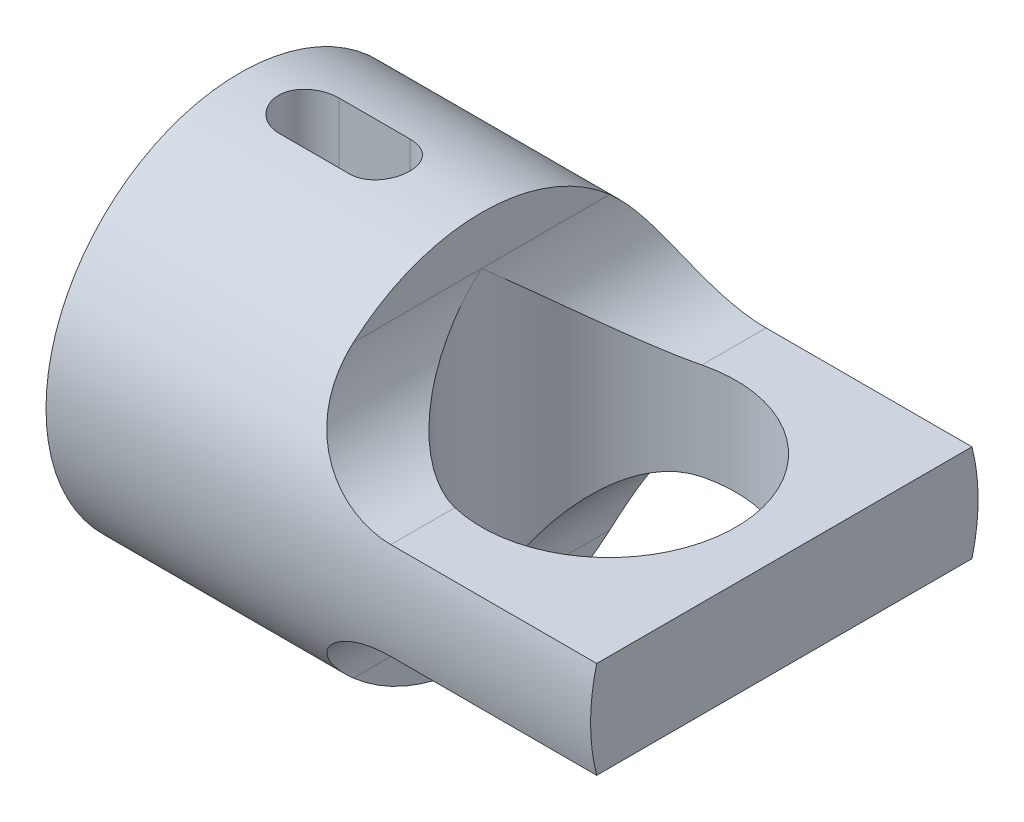
SolidWorks part; units mm, degrees
note: The reader was unsure of these and kept them because the rebuilt part matched: shared geometry of "Sketch2<3>".
material "AISI 4340 Steel, annealed"
ref_plane "Front Plane" through (0, 0, 0) normal (0, 0, 1) x (1, 0, 0)
ref_plane "Top Plane" through (0, 0, 0) normal (0, 1, 0) x (1, 0, 0)
ref_plane "Right Plane" through (0, 0, 0) normal (1, 0, 0) x (0, 0, -1)
sketch "Sketch1" plane through (0, 0, 0) normal (0, 1, 0) x (1, 0, 0)
  line L0 (0, 0) -> (0, 558.8) construction
  line L1 (355.6, -292.1) -> (-355.6, -292.1)
  line L2 (355.6, -292.1) -> (355.6, 292.1)
  line L3 (355.6, 292.1) -> (-355.6, 292.1)
  line L4 (-355.6, -292.1) -> (-355.6, 292.1)
  line L5 (355.6, -292.1) -> (-355.6, 292.1) construction
  line L6 (355.6, 292.1) -> (-355.6, -292.1) construction
  line L7 (-355.6, 508) -> (355.6, 508)
  line L8 (-355.6, 508) -> (-355.6, 558.8)
  line L9 (-355.6, 558.8) -> (355.6, 558.8)
  line L10 (355.6, 508) -> (355.6, 558.8)
  line L11 (-355.6, 508) -> (-355.6, 292.1) construction
  line L12 (355.6, 508) -> (355.6, 292.1) construction
  line L13 (-355.6, 0) -> (355.6, 0) construction
  line L14 (-294.9829, 0) -> (-294.9829, 558.8) construction
  line L15 (294.9829, 0) -> (294.9829, 558.8) construction
  line L16 (-294.9829, 534.9875) -> (0, 531.8125) construction
  line L17 (-294.7945, 552.4935) -> (0.1884, 549.3185)
  line L18 (-295.1713, 517.4815) -> (-0.1884, 514.3065)
  line L19 (0, 531.8125) -> (294.9829, 534.9875) construction
  line L20 (-0.1884, 549.3185) -> (294.7945, 552.4935)
  line L21 (0.1884, 514.3065) -> (295.1713, 517.4815)
  line L22 (-355.6, 292.1) -> (-355.6, 342.9)
  line L23 (-358.775, 342.9) -> (-330.2, 342.9)
  line L24 (-330.2, 342.9) -> (-330.2, 292.1)
  line L25 (-101.6, 558.8) -> (-101.6, 0) construction
  line L26 (-333.0829, 293.6875) -> (-256.8829, 293.6875)
  line L27 (-333.0829, 293.6875) -> (-333.0829, 331.7875)
  line L28 (-333.0829, 331.7875) -> (-256.8829, 331.7875)
  line L29 (-256.8829, 293.6875) -> (-256.8829, 331.7875)
  line L30 (-333.0829, 293.6875) -> (-256.8829, 331.7875) construction
  line L31 (-333.0829, 331.7875) -> (-256.8829, 293.6875) construction
  line L32 (358.775, 342.9) -> (0, 380.3316)
  line L33 (-330.2, 326.4184) -> (0, 361.1763)
  line L34 (-114.3, 292.1) -> (-114.3, 368.3)
  line L35 (-355.6, 558.8) -> (-355.6, 762) construction
  line L36 (-88.9, 292.1) -> (-88.9, 368.3)
  line L37 (-114.3, 292.1) -> (-88.9, 368.3) construction
  line L38 (-114.3, 368.3) -> (-88.9, 292.1) construction
  line L39 (330.2, 326.726) -> (0, 361.1763)
  line L40 (-355.6, 762) -> (355.6, 762)
  line L41 (-355.6, 241.3) -> (355.6, 241.3)
  line L42 (-330.2, 342.9) -> (-330.2, 561.975) construction
  line L43 (-38.1, 293.6875) -> (38.1, 293.6875)
  line L44 (-38.1, 293.6875) -> (-38.1, 357.1875)
  line L45 (-38.1, 357.1875) -> (38.1, 357.1875)
  line L46 (38.1, 293.6875) -> (38.1, 357.1875)
  line L47 (-38.1, 293.6875) -> (38.1, 357.1875) construction
  line L48 (-38.1, 357.1875) -> (38.1, 293.6875) construction
  line L49 (-330.2, 561.975) -> (-358.775, 561.975)
  line L50 (-358.775, 342.9) -> (-358.775, -342.9)
  line L51 (-355.6, 579.4375) -> (358.775, 579.4375)
  line L52 (-330.2, 292.1) -> (-330.2, -342.9)
  line L53 (-330.2, -342.9) -> (-358.775, -342.9)
  line L54 (-355.6, 342.9) -> (0, 380.3316)
  line L55 (-330.2, 326.4184) -> (-355.6, 323.7448) construction
  line L56 (-114.3, 368.3) -> (-88.9, 368.3)
  line L57 (330.2, 292.1) -> (330.2, 342.9)
  line L58 (330.2, 342.9) -> (358.775, 342.9)
  line L59 (358.775, 342.9) -> (358.775, -342.9)
  line L60 (330.2, 342.9) -> (330.2, 561.975)
  line L61 (330.2, 561.975) -> (358.775, 561.975)
  line L62 (358.775, -342.9) -> (330.2, -342.9)
  line L63 (330.2, -342.9) -> (330.2, -292.1)
  line L64 (355.6, 762) -> (355.6, 558.8) construction
  line L65 (-355.6, 762) -> (-355.6, 812.8)
  line L66 (-355.6, 812.8) -> (355.6, 812.8)
  line L67 (355.6, 812.8) -> (355.6, 762)
  line L68 (-21.2236, 223.9178) -> (-84.7236, 223.9178)
  line L69 (-21.2236, 223.9178) -> (-21.2236, 333.1378)
  line L70 (-21.2236, 333.1378) -> (-84.7236, 333.1378)
  line L71 (-84.7236, 223.9178) -> (-84.7236, 333.1378)
  line L72 (-312.49, 247.65) -> (-277.4759, 247.65)
  line L73 (-312.49, 247.65) -> (-312.49, 285.75)
  line L74 (-312.49, 285.75) -> (-277.4759, 285.75)
  line L75 (-277.4759, 247.65) -> (-277.4759, 285.75)
  line L76 (-312.49, 247.65) -> (-277.4759, 285.75) construction
  line L77 (-312.49, 285.75) -> (-277.4759, 247.65) construction
  line L78 (-114.3, 598.4875) -> (-355.6, 598.4875)
  line L79 (-355.6, 598.4875) -> (-355.6, 579.4375)
  line L80 (-114.3, 508) -> (-114.3, 598.4875)
  line L81 (-114.3, 598.4875) -> (-88.9, 598.4875)
  line L82 (-88.9, 508) -> (-88.9, 598.4875)
  line L83 (-114.3, 508) -> (-88.9, 598.4875) construction
  line L84 (-114.3, 598.4875) -> (-88.9, 508) construction
  line L85 (358.775, 579.4375) -> (358.775, 598.4875)
  line L86 (-88.9, 598.4875) -> (358.775, 598.4875)
  line L87 (358.775, 561.975) -> (358.775, 504.825)
  line L88 (358.775, 504.825) -> (-358.775, 504.825)
  line L89 (-358.775, 504.825) -> (-358.775, 561.975)
  line L90 (-355.6, 558.8) -> (-358.775, 558.8)
  line L91 (-355.6, 292.1) -> (-355.6, 342.9)
  line L92 (-355.6, 292.1) -> (-358.775, 292.1)
  line L93 (355.6, 558.8) -> (358.775, 558.8)
  line L94 (-355.6, -292.1) -> (-358.775, -292.1)
  line L95 (-355.6, -292.1) -> (-355.6, -342.9)
  line L96 (355.6, -292.1) -> (358.775, -292.1)
  line L97 (355.6, -292.1) -> (355.6, -342.9)
  line L98 (0, 531.8125) -> (0, 812.8) construction
  line L99 (-294.9829, 534.9875) -> (-294.9829, 812.8) construction
  line L100 (294.9829, 534.9875) -> (294.9829, 812.8) construction
  line L101 (-355.6, 751.5377) -> (355.6, 743.8829) construction
  line L102 (355.6, 751.5377) -> (0, 747.7103) construction
  line L103 (224.9153, 774.1325) -> (294.9829, 788.9875)
  line L104 (-355.6, 753.5075) -> (355.6, 722.339) construction
  line L105 (0, 785.8125) -> (-2.0947, 738.015) construction
  line L106 (224.9153, 774.1325) -> (177.8, 788.9875) construction
  line L107 (223.1136, 769.3102) -> (177.8, 788.9875) construction
  line L108 (211.3067, 752.6857) -> (177.8, 788.9875) construction
  line L109 (131.699, 840.6975) -> (135.001, 840.6975)
  line L110 (224.9153, 774.1325) -> (211.3067, 752.6857)
  line L111 (177.8, 788.9875) -> (177.8, 838.3891) construction
  line L112 (218.111, 763.4091) -> (177.8, 788.9875) construction
  line L113 (190.5, 836.7288) -> (165.1, 836.7288)
  line L114 (165.1, 836.7288) -> (177.8, 788.9875)
  line L115 (177.8, 788.9875) -> (190.5, 836.7288)
  line L116 (355.6, 812.8) -> (355.6, 852.4875)
  line L117 (355.6, 852.4875) -> (330.2, 852.4875)
  line L118 (330.2, 852.4875) -> (330.2, 812.8)
  line L119 (261.0328, 817.6788) -> (294.9829, 788.9875)
  line L120 (114.3, 852.4875) -> (88.9, 852.4875)
  line L121 (114.3, 852.4875) -> (114.3, 762)
  line L122 (218.2338, 855.7788) -> (257.8578, 855.7788)
  line L123 (88.9, 852.4875) -> (88.9, 762)
  line L124 (114.3, 852.4875) -> (88.9, 762) construction
  line L125 (114.3, 762) -> (88.9, 852.4875) construction
  line L126 (218.2338, 855.7788) -> (218.2338, 817.6788)
  line L127 (218.2338, 817.6788) -> (257.8578, 817.6788)
  line L128 (257.8578, 855.7788) -> (257.8578, 817.6788)
  line L129 (218.2338, 855.7788) -> (257.8578, 817.6788) construction
  line L130 (218.2338, 817.6788) -> (257.8578, 855.7788) construction
  line L131 (261.0328, 836.7288) -> (355.6, 836.7288)
  line L132 (261.0328, 840.6975) -> (355.6, 840.6975)
  line L133 (261.0328, 832.76) -> (355.6, 832.76)
  line L134 (257.8578, 817.6788) -> (261.0328, 817.6788)
  line L135 (261.0328, 817.6788) -> (261.0328, 855.7788)
  line L136 (261.0328, 855.7788) -> (257.8578, 855.7788)
  line L137 (294.9829, 827.0875) -> (294.9829, 832.76)
  line L138 (261.0328, 846.2538) -> (270.5578, 846.2538)
  line L139 (270.5578, 846.2538) -> (270.5578, 827.2038)
  line L140 (270.5578, 827.2038) -> (261.0328, 827.2038)
  line L141 (218.2338, 836.7288) -> (214.9318, 836.7288)
  line L142 (214.9318, 836.7288) -> (214.9318, 840.6975)
  line L143 (214.9318, 840.6975) -> (218.2338, 840.6975)
  line L144 (214.9318, 836.7288) -> (214.9318, 832.76)
  line L145 (214.9318, 832.76) -> (218.2338, 832.76)
  line L146 (177.8, 788.9875) -> (170.137, 837.7912)
  line L147 (135.001, 839.1418) -> (144.526, 839.1418)
  line L148 (144.526, 839.1418) -> (144.526, 834.3158)
  line L149 (92.075, 855.7788) -> (131.699, 855.7788)
  line L150 (92.075, 855.7788) -> (92.075, 817.6788)
  line L151 (92.075, 817.6788) -> (131.699, 817.6788)
  line L152 (131.699, 855.7788) -> (131.699, 817.6788)
  line L153 (92.075, 855.7788) -> (131.699, 817.6788) construction
  line L154 (92.075, 817.6788) -> (131.699, 855.7788) construction
  line L155 (135.001, 840.6975) -> (135.001, 832.76)
  line L156 (135.001, 832.76) -> (131.699, 832.76)
  line L157 (144.526, 834.3158) -> (135.001, 834.3158)
  line L158 (135.001, 830.3788) -> (154.051, 830.3788)
  line L159 (154.051, 830.3788) -> (154.051, 843.0788)
  line L160 (154.051, 843.0788) -> (135.001, 843.0788)
  line L161 (135.001, 843.0788) -> (135.001, 840.6975)
  line L162 (135.001, 832.76) -> (135.001, 830.3788)
  line L163 (144.526, 839.1418) -> (146.1135, 839.1418)
  line L164 (146.1135, 839.1418) -> (146.1135, 834.3158)
  line L165 (146.1135, 834.3158) -> (144.526, 834.3158)
  line L166 (150.0823, 836.7288) -> (155.1193, 836.7288) construction
  line L168 (150.4791, 834.7444) -> (155.1193, 834.7444)
  line L169 (145.9562, 849.4288) -> (145.9562, 824.0288)
  line L170 (145.9562, 824.0288) -> (181.6464, 824.0288)
  line L171 (181.6464, 824.0288) -> (181.6464, 849.4288)
  line L172 (181.6464, 849.4288) -> (145.9562, 849.4288)
  line L173 (154.051, 843.0788) -> (159.088, 843.0788)
  line L174 (159.088, 843.0788) -> (159.088, 830.3788)
  line L175 (159.088, 830.3788) -> (154.051, 830.3788)
  line L176 (135.001, 843.0788) -> (135.001, 849.4288)
  line L177 (135.001, 849.4288) -> (138.176, 849.4288)
  line L178 (138.176, 849.4288) -> (138.176, 824.0288)
  line L179 (138.176, 824.0288) -> (135.001, 824.0288)
  line L180 (135.001, 824.0288) -> (135.001, 830.3788)
  line L181 (138.176, 845.9998) -> (139.7635, 845.9998)
  line L182 (139.7635, 845.9998) -> (139.7635, 827.4578)
  line L183 (139.7635, 827.4578) -> (138.176, 827.4578)
  line L184 (145.9562, 845.9998) -> (144.8005, 845.9998)
  line L185 (144.8005, 845.9998) -> (144.8005, 827.4578)
  line L186 (144.8005, 827.4578) -> (145.9562, 827.4578)
  line L187 (150.4791, 838.7132) -> (155.1193, 838.7132)
  arc A0 (-294.7945, 552.4935) -> (-295.1713, 517.4815) centre (-294.9829, 534.9875) ccw
  arc A1 (-0.1884, 514.3065) -> (0.1884, 549.3185) centre (0, 531.8125) ccw
  circle A2 centre (-294.9829, 534.9875) radius 38.1
  circle A3 centre (0, 531.8125) radius 38.1
  circle A4 centre (294.9829, 534.9875) radius 38.1
  arc A5 (-0.1884, 549.3185) -> (0.1884, 514.3065) centre (0, 531.8125) ccw
  arc A6 (295.1713, 517.4815) -> (294.7945, 552.4935) centre (294.9829, 534.9875) ccw
  circle A7 centre (-294.9829, 534.9875) radius 44.45
  circle A8 centre (-294.9829, 788.9875) radius 38.1
  circle A9 centre (294.9829, 788.9875) radius 38.1
  circle A10 centre (0, 785.8125) radius 38.1
  circle A11 centre (224.9153, 774.1325) radius 24 construction
  circle A12 centre (177.8, 788.9875) radius 49.4016 construction
  circle A13 centre (150.0823, 836.7288) radius 1.5875
  circle A14 centre (211.3067, 752.6857) radius 24
  circle A15 centre (223.1136, 769.3102) radius 24
  arc A17 (155.1193, 834.7444) -> (155.1193, 838.7132) centre (155.1193, 836.7288) ccw
  circle A18 centre (170.137, 836.7288) radius 8.3344
  arc A19 (150.4791, 834.7444) -> (150.4791, 838.7132) centre (150.4791, 836.7288) cw
  point P0 (0, 0)
  point P12 (0, 531.8125)
  point P14 (-294.9829, 534.9875)
  point P20 (294.9829, 534.9875)
  point P23 (-147.4915, 533.4)
  point P34 (147.4915, 533.4)
  point P41 (-294.9829, 312.7375)
  point P49 (-101.6, 330.2)
  point P62 (0, 325.4375)
  point P91 (-294.9829, 266.7)
  point P96 (-101.6, 553.2437)
  point P131 (111.887, 836.7288)
  point P147 (101.6, 807.2438)
  point P152 (238.0458, 836.7288)
  point P184 (135.001, 836.7288)
  point P189 (144.526, 836.7288)
  point P193 (154.051, 836.7288)
  point P199 (152.6008, 836.7288)
  point P210 (181.6464, 836.7288)
  point P220 (139.7635, 836.7288)
  point P229 (148.4948, 836.7288)
  dimension "D4" = 26.9875
  dimension "D6" = 26.9875
  dimension "D7" = 17.507
  dimension "D8" = 700
  dimension "D9" = 76.2
  dimension "D26" = 3.175
  dimension "D33" = 44.45
  dimension "D35" = 88.9
  dimension "D40" = 76.2
  dimension "D38" = 48
  dimension "D43" = 26.9875
  dimension "D65" = 39.624
  dimension "D75" = 3.175
  dimension "D78" = 1.9844
  dimension "D88" = 16.6687
  dimension "D89" = 11.5094
  dimension "D2" = 711.2
  dimension "D3" = 50.8
  dimension "D5" = 558.8
  dimension "D10" = 50.8
  dimension "D11" = 28.575
  dimension "D12" = 76.2
  dimension "D13" = 38.1
  dimension "D14" = 1.5875
  dimension "D15" = 294.9829
  dimension "D16" = 3.175
  dimension "D17" = 25.4
  dimension "D18" = 76.2
  dimension "D19" = 19.05
  dimension "D20" = 50.8
  dimension "D21" = 63.5
  dimension "D22" = 3.175
  dimension "D23" = 3.175
  dimension "D24" = 50.8
  dimension "D25" = 241.3
  dimension "D27" = 63.5
  dimension "D28" = 109.22
  dimension "D29" = 38.1
  dimension "D30" = 25.4
  dimension "D31" = 35.0141
  dimension "D32" = 19.05
  dimension "D34" = 101.6
  dimension "D36" = 50.8
  dimension "D37" = 203.2
  dimension "D39" = 26.9875
  dimension "D41" = 26.9875
  dimension "D42" = 71.625
  dimension "D44" = 177.8
  dimension "D45" = 25.4
  dimension "D46" = 5.973
  dimension "D47" = 3.302
  dimension "D48" = 25.4
  dimension "D49" = 90.4875
  dimension "D50" = 25.4
  dimension "D51" = 101.6
  dimension "D52" = 25.4
  dimension "D53" = 90.4875
  dimension "D54" = 39.624
  dimension "D55" = 38.1
  dimension "D56" = 3.175
  dimension "D57" = 44.45
  dimension "D58" = 7.9375
  dimension "D59" = 3.9688
  dimension "D60" = 5.6725
  dimension "D61" = 9.525
  dimension "D62" = 19.05
  dimension "D63" = 9.525
  dimension "D64" = 7.9375
  dimension "D66" = 5.973
  dimension "D67" = 4.826
  dimension "D68" = 38.1
  dimension "D69" = 3.175
  dimension "D70" = 7.9375
  dimension "D71" = 3.302
  dimension "D72" = 9.525
  dimension "D73" = 12.7
  dimension "D74" = 19.05
  dimension "D76" = 3.9688
  dimension "D77" = 1.5875
  dimension "D79" = 5.037
  dimension "D80" = 5.037
  dimension "D81" = 5.037
  dimension "D82" = 25.4
  dimension "D83" = 3.175
  dimension "D84" = 18.542
  dimension "D85" = 1.5875
  dimension "D86" = 7.7802
  dimension "D87" = 5.037
sketch "Sketch2" plane through (0, 0, 0) normal (0, 1, 0) x (1, 0, 0)
  line L0 (144.8005, 845.9998) -> (144.8005, 827.4578) construction
  line L1 (145.9562, 845.9998) -> (144.8005, 845.9998) construction
  line L2 (145.9562, 849.4288) -> (145.9562, 824.0288) construction
  line L3 (181.6464, 849.4288) -> (145.9562, 849.4288) construction
  line L4 (181.6464, 824.0288) -> (181.6464, 849.4288) construction
  line L5 (150.4791, 838.7132) -> (155.1193, 838.7132) construction
  line L6 (150.4791, 834.7444) -> (155.1193, 834.7444) construction
  line L7 (159.088, 843.0788) -> (159.088, 830.3788) construction
  line L9 (144.8005, 845.9998) -> (144.8005, 836.7288)
  line L10 (145.9562, 845.9998) -> (144.8005, 845.9998)
  line L11 (145.9562, 849.4288) -> (145.9562, 845.9998)
  line L12 (181.6464, 849.4288) -> (145.9562, 849.4288)
  line L13 (181.6464, 836.7288) -> (181.6464, 849.4288)
  line L14 (150.0823, 836.7288) -> (155.1193, 836.7288) construction
  line L15 (150.4791, 838.7132) -> (155.1193, 838.7132)
  line L16 (159.088, 843.0788) -> (159.088, 830.3788)
  line L17 (150.4791, 834.7444) -> (155.1193, 834.7444)
  line L20 (144.8005, 836.7288) -> (181.6464, 836.7288)
  arc A1 (150.4791, 838.7132) -> (150.4791, 834.7444) centre (150.4791, 836.7288) ccw construction
  arc A3 (155.1193, 834.7444) -> (155.1193, 838.7132) centre (155.1193, 836.7288) ccw construction
  circle A4 centre (170.137, 836.7288) radius 8.3344 construction
  circle A5 centre (170.137, 836.7288) radius 8.3344
  arc A6 (150.4791, 838.7132) -> (150.4791, 834.7444) centre (150.4791, 836.7288) ccw
  arc A7 (155.1193, 834.7444) -> (155.1193, 838.7132) centre (155.1193, 836.7288) ccw
revolve "Revolve1" add sketch "Sketch2" angle 360 about L20
extrude "Cut-Extrude1" cut sketch "Sketch2<3>" against normal through all both and the other way through all contours L20 A7 L15 A6 | L17 A7 L20 A6
sketch "Sketch2<3>" plane through (0, 0, 0) normal (0, 1, 0) x (1, 0, 0) same geometry as "Sketch2"
sketch "Sketch3" plane through (144.8005, 0, 0) normal (-1, 0, 0) x (0, 0, 1)
  circle A0 centre (-836.7288, 0) radius 9.271 construction
  circle A1 centre (-836.7288, 0) radius 9.271
  circle A2 centre (-836.7288, 0) radius 6.4492
  dimension "D1" = 12.8984
extrude "Cut-Extrude2" cut sketch "Sketch3" against normal up to vertex (14.2875 mm away) contours A2 up to point (159.088, 0, -843.0788)
ref_plane "Plane1" through (0, 0, -824.0288) normal (0, 0, 1) x (1, 0, 0)
sketch "Sketch5" plane through (0, 0, -824.0288) normal (0, 0, 1) x (1, 0, 0)
  line L0 (181.6464, -12.7) -> (181.6464, 12.7) construction
  line L1 (181.6464, -12.7) -> (181.6464, 12.7)
  line L2 (181.6464, 3.175) -> (168.1527, 3.175)
  line L3 (161.8027, 9.525) -> (161.8027, 12.7)
  line L4 (161.8027, 12.7) -> (181.6464, 12.7)
  line L5 (181.6464, -12.7) -> (161.8027, -12.7)
  line L6 (161.8027, -12.7) -> (161.8027, -9.525)
  line L7 (168.1527, -3.175) -> (181.6464, -3.175)
  arc A0 (161.8027, -9.525) -> (168.1527, -3.175) centre (168.1527, -9.525) cw
  arc A1 (161.8027, 9.525) -> (168.1527, 3.175) centre (168.1527, 9.525) ccw
  point P12 (161.8027, 3.175)
  dimension "D3" = 6.35
  dimension "D1" = 19.8438
  dimension "D2" = 9.525
extrude "Cut-Extrude4" cut sketch "Sketch5" against normal through all contours L3 A1 L2 L1 L4 | A0 L6 L5 L1 L7
equation "\"D4@Sketch1\"=1+(1/8)/2"
equation "\"D6@Sketch1\"=\"D4@Sketch1\""
equation "\"D7@Sketch1\"=22*5mm/pi/2"
equation "\"D8@Sketch1\"=140*5mm"
equation "\"D31@Sketch1\"=\"D7@Sketch1\"*2"
equation "\"D38@Sketch1\"=48mm"
equation "\"D42@Sketch1\"=(\"D38@Sketch1\"+3)/2+3/8"
equation "\"D57@Sketch1\"=1.5+1/4"
equation "\"D86@Sketch1\"=.333-(.333-.108-\"D81@Sketch1\")"
equation "\"D87@Sketch1\"=\"D81@Sketch1\""
equation "\"D79@Sketch1\"=\"D81@Sketch1\""
